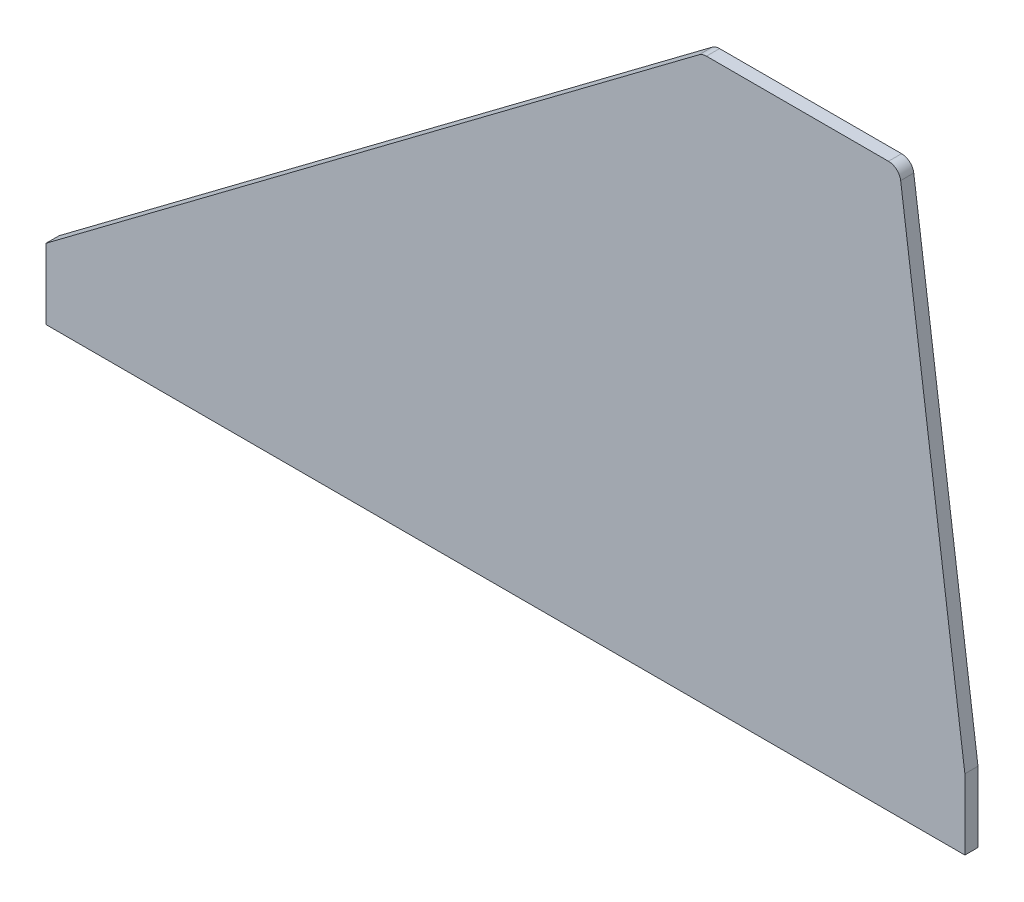
SolidWorks part; units mm, degrees
material "E-Glass Fiber"
ref_plane "Front Plane" through (0, 0, 0) normal (0, 0, 1) x (1, 0, 0)
ref_plane "Top Plane" through (0, 0, 0) normal (0, 1, 0) x (1, 0, 0)
ref_plane "Right Plane" through (0, 0, 0) normal (1, 0, 0) x (0, 0, -1)
sketch "Fin Profile" plane through (0, 0, 0) normal (0, 0, 1) x (1, 0, 0)
  line L0 (355.6, -27.2542) -> (0, -27.2542)
  line L1 (0, -27.2542) -> (0, 0)
  line L2 (0, 0) -> (254, 190.5)
  line L3 (254, 190.5) -> (330.2, 190.5)
  line L5 (330.2, 190.5) -> (355.6, 0)
  line L6 (355.6, 0) -> (355.6, -27.2542)
  dimension "D1" = 27.2542
  dimension "D2" = 355.6
  dimension "D3" = 76.2
  dimension "D4" = 254
  dimension "D5" = 190.5
extrude "Fin Body" add sketch "Fin Profile" along normal blind 5.08 contours L2 L3 L5 L6 L0 L1
fillet "Fin Fillets" radius 4.7625 2 edges at (330.2, 190.5, 2.54) (254, 190.5, 2.54)
equation "\"Root Chord\"= 14"
equation "\"Span\"= 7.5"
equation "\"Tip Chord\"= 3"
equation "\"Sweep Distance\"= 10"
equation "\"Fin Thickness\"= 0.2"
equation "\"Tab Height\"=1"
equation "\"D1@Fin Profile\"=\"Tab Height\" + (0.17/2) - (0.012)"
equation "\"D2@Fin Profile\" = \"Root Chord\""
equation "\"D3@Fin Profile\" = \"Tip Chord\""
equation "\"D4@Fin Profile\" = \"Sweep Distance\""
equation "\"D5@Fin Profile\" = \"Span\""
equation "\"Fillet Radius\"=0.1875"
equation "\"D1@Fin Fillets\" = \"Fillet Radius\""
equation "\"D1@Fin Body\"=\"Fin Thickness\""
